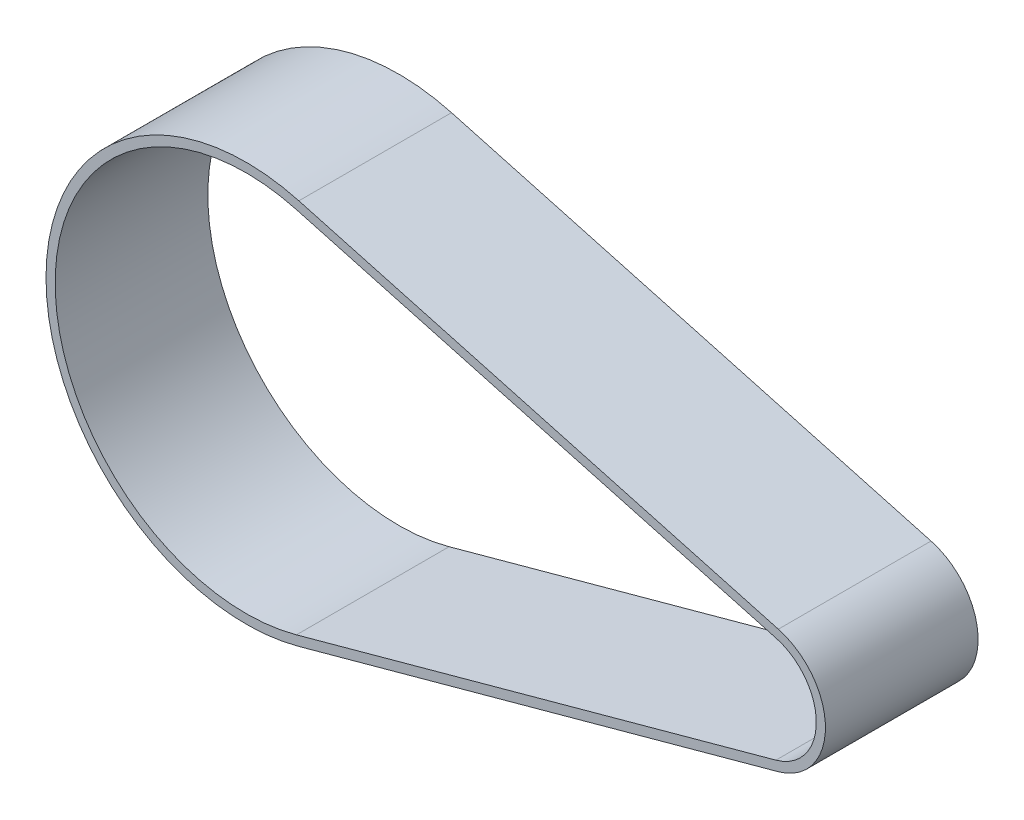
SolidWorks part; units mm, degrees
material "Rubber"
ref_plane "Front Plane" through (0, 0, 0) normal (0, 0, 1) x (1, 0, 0)
ref_plane "Top Plane" through (0, 0, 0) normal (0, 1, 0) x (1, 0, 0)
ref_plane "Right Plane" through (0, 0, 0) normal (1, 0, 0) x (0, 0, -1)
sketch "Sketch1" plane through (0, 0, 0) normal (0, 0, 1) x (1, 0, 0)
  line L0 (13.75, 0) -> (-13.75, 0) construction
  line L1 (-76.1479, 30.1511) -> (2.3706, 8.6615)
  line L2 (-76.1479, -30.1511) -> (2.3706, -8.6615)
  line L3 (-75.7519, 31.5979) -> (2.7665, 10.1083)
  line L4 (-75.7519, -31.5979) -> (2.7665, -10.1083)
  arc A0 (-76.1479, 30.1511) -> (-76.1479, -30.1511) centre (-84.4, 0) ccw
  arc A1 (2.3706, -8.6615) -> (2.3706, 8.6615) centre (0, 0) ccw
  arc A2 (2.7665, -10.1083) -> (2.7665, 10.1083) centre (0, 0) ccw
  arc A3 (-75.7519, 31.5979) -> (-75.7519, -31.5979) centre (-84.4, 0) ccw
  arc A4 (2.3706, -8.6615) -> (2.3706, 8.6615) centre (0, 0) ccw construction
  circle A5 centre (-84.4, 0) radius 34.7298 construction
  arc A6 (-90.4737, 30.6643) -> (-94.252, 29.6669) centre (-84.4, 0) ccw construction
  arc A7 (8.2209, 3.6135) -> (7.7681, 4.5052) centre (0, 0) ccw construction
  dimension "D1" = 1.5
extrude "Boss-Extrude1" add sketch "Sketch1" along normal blind 25
